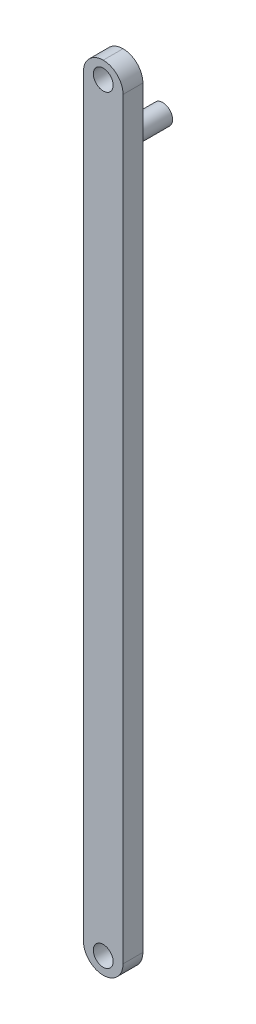
SolidWorks part; units mm, degrees
ref_plane "Front" through (0, 0, 0) normal (0, 0, 1) x (1, 0, 0)
ref_plane "Top" through (0, 0, 0) normal (0, 1, 0) x (1, 0, 0)
ref_plane "Right" through (0, 0, 0) normal (1, 0, 0) x (0, 0, -1)
sketch "Sketch1" plane through (0, 0, 0) normal (0, 0, 1) x (1, 0, 0)
  line L1 (-10, -200) -> (10, -200)
  line L2 (-10, -200) -> (-10, 200)
  line L3 (-10, 200) -> (10, 200)
  line L4 (10, -200) -> (10, 200)
  line L5 (-10, -200) -> (10, 200) construction
  line L6 (-10, 200) -> (10, -200) construction
  point P0 (0, 0)
  dimension "D1" = 400
  dimension "D2" = 20
extrude "Boss-Extrude1" add sketch "Sketch1" along normal blind 10
fillet "Fillet1" radius 10 4 edges at (-10, -200, 5) (10, -200, 5) (-10, 200, 5) (10, 200, 5)
sketch "Sketch2" plane through (0, 0, 10) normal (0, 0, 1) x (1, 0, 0)
  line L0 (-10, 190) -> (-10, -190) construction
  circle A0 centre (0, 191.5) radius 5
  arc A1 (0, 200) -> (-10, 190) centre (0, 190) ccw construction
  dimension "D1" = 10
  dimension "D2" = 1.5
  dimension "D3" = 10
extrude "Cut-Extrude1" cut sketch "Sketch2" against normal through all
mirror "Mirror1" about plane through (0, 0, 0) normal (0, 1, 0) of "Cut-Extrude1"
sketch "Sketch3" plane through (0, 0, 0) normal (0, 0, -1) x (-1, 0, 0)
  circle A0 centre (0, 161.5) radius 5
  circle A1 centre (0, 191.5) radius 5 construction
  dimension "D1" = 10
  dimension "D2" = 30
extrude "Boss-Extrude2" add sketch "Sketch3" along normal blind 20
fillet "Fillet2" radius 5 1 edges at (-5, 161.5, 0)
